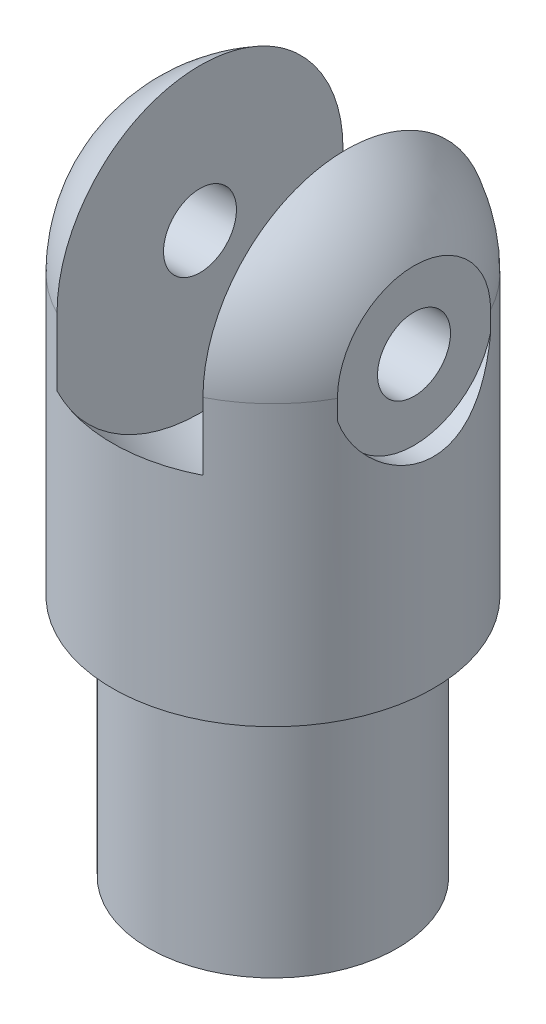
SolidWorks part; units mm, degrees
ref_plane "Front Plane" through (0, 0, 0) normal (0, 0, 1) x (1, 0, 0)
ref_plane "Top Plane" through (0, 0, 0) normal (0, 1, 0) x (1, 0, 0)
ref_plane "Right Plane" through (0, 0, 0) normal (1, 0, 0) x (0, 0, -1)
sketch "Sketch1" plane through (0, 0, 0) normal (0, 1, 0) x (1, 0, 0)
  circle A0 centre (0, 0) radius 12.9794
  dimension "D1" = 25.9588
extrude "Boss-Extrude1" add sketch "Sketch1" along normal blind 25.4 contours A0
sketch "Sketch2" plane through (0, 0, 0) normal (1, 0, 0) x (0, 0, -1)
  line L0 (-16.764, 25.4) -> (-16.764, 54.61)
  line L1 (0, 25.4) -> (-16.764, 25.4)
  line L4 (12.9794, 25.4) -> (-12.9794, 25.4) construction
  line L5 (0, 18.4404) -> (0, -18.4404) construction
  line L6 (0, 25.4) -> (0, 71.374)
  arc A0 (0, 71.374) -> (-16.764, 54.61) centre (0, 54.61) ccw
  dimension "D1" = 33.528
  dimension "D2" = 29.21
revolve "Revolve1" add sketch "Sketch2" angle 360 about L6
sketch "Sketch3" plane through (0, 0, 0) normal (1, 0, 0) x (0, 0, -1)
  line L2 (16.764, 54.61) -> (-16.764, 54.61) construction
  circle A2 centre (0, 54.61) radius 3.81
extrude "Cut-Extrude1" cut sketch "Sketch3" against normal through all both and the other way through all
sketch "Sketch4" plane through (0, 0, 0) normal (0, 0, 1) x (1, 0, 0)
  line L0 (16.3253, 54.61) -> (-16.3253, 54.61) construction
  line L1 (-7.62, 38.1) -> (-7.62, 54.61)
  line L2 (-7.62, 54.61) -> (7.62, 54.61)
  line L3 (7.62, 54.61) -> (7.62, 38.1)
  arc A0 (-7.62, 38.1) -> (7.62, 38.1) centre (0, 54.61) ccw
  dimension "D1" = 15.24
  dimension "D2" = 16.51
revolve "Cut-Revolve1" cut sketch "Sketch4" angle 360 about L2
ref_plane "Plane1" through (16.764, 0, 0) normal (1, 0, 0) x (0, 0, -1)
sketch "Sketch6" plane through (16.764, 0, 0) normal (1, 0, 0) x (0, 0, -1)
  circle A0 centre (0, 54.61) radius 8.255
extrude "Cut-Extrude2" cut sketch "Sketch6" against normal blind 2.032
mirror "Mirror1" about plane through (0, 0, 0) normal (1, 0, 0) of "Cut-Extrude2"
ref_plane "Plane3" through (0, 30.48, 0) normal (0, 1, 0) x (1, 0, 0)
sketch "Sketch7" plane through (0, 30.48, 0) normal (0, 1, 0) x (1, 0, 0)
  circle A0 centre (0, 0) radius 3.81
  circle A1 centre (0, 0) radius 1.905
extrude "Cut-Extrude3" cut sketch "Sketch7" along normal blind 26.67 contours A1 | A0 A1 region at (-3.7022, 30.48, 0) region at (0, 30.48, 0)
extrude "Cut-Extrude4" cut sketch "Sketch7<3>" against normal through all contours A1 region at (0, 30.48, 0)
sketch "Sketch7<3>" plane through (0, 30.48, 0) normal (0, 1, 0) x (1, 0, 0) same geometry as "Sketch7"
